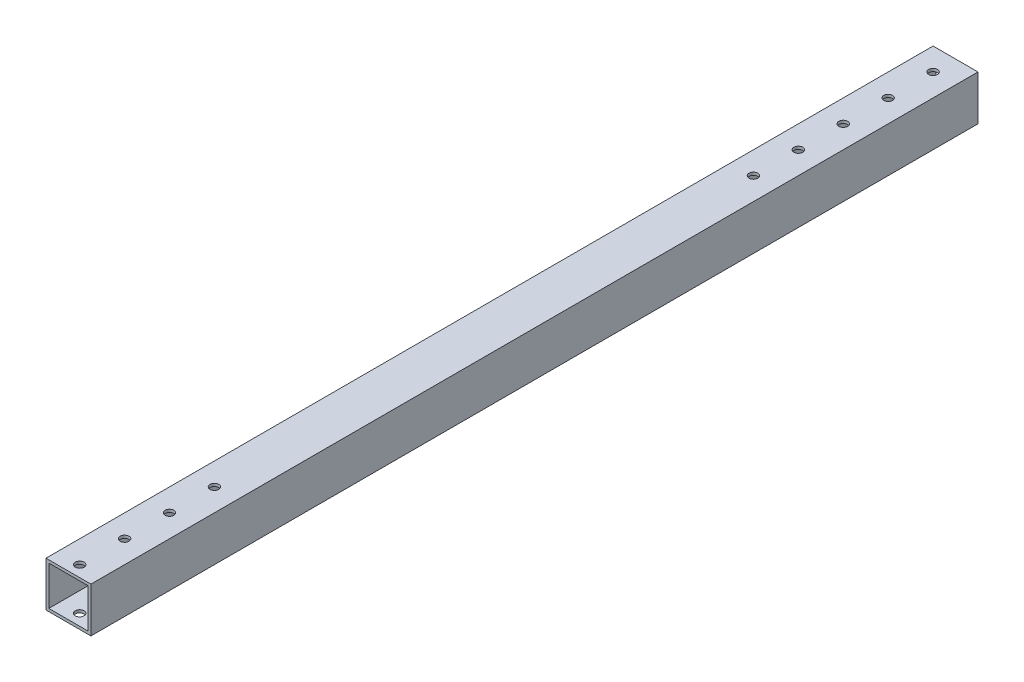
SolidWorks part; units mm, degrees
material "6061-T6 (SS)"
ref_plane "Front Plane" through (0, 0, 0) normal (0, 0, 1) x (1, 0, 0)
ref_plane "Top Plane" through (0, 0, 0) normal (0, 1, 0) x (1, 0, 0)
ref_plane "Right Plane" through (0, 0, 0) normal (1, 0, 0) x (0, 0, -1)
sketch "Sketch1" plane through (0, 0, 0) normal (0, 0, 1) x (1, 0, 0)
  line L1 (-12.7, -12.7) -> (12.7, -12.7)
  line L2 (-12.7, -12.7) -> (-12.7, 12.7)
  line L3 (-12.7, 12.7) -> (12.7, 12.7)
  line L4 (12.7, -12.7) -> (12.7, 12.7)
  line L5 (-12.7, -12.7) -> (12.7, 12.7) construction
  line L6 (-12.7, 12.7) -> (12.7, -12.7) construction
  point P0 (0, 0)
  dimension "D1" = 25.4
  dimension "D2" = 25.4
extrude "Boss-Extrude1" add sketch "Sketch1" along normal mid plane 501.65
shell "Shell1" thickness 1.5875 removed face at (0, 0, -250.825) removed face at (0, 0, 250.825)
sketch "Sketch3" plane through (0, 0, 0) normal (0, 1, 0) x (1, 0, 0)
  line L0 (12.7, 250.825) -> (-12.7, 250.825) construction
  circle A0 centre (0, 238.125) radius 2.4892
  circle A1 centre (0, 212.725) radius 2.4892
  circle A2 centre (0, 187.325) radius 2.4892
  circle A3 centre (0, 161.925) radius 2.4892
  circle A4 centre (0, 136.525) radius 2.4892
  circle A5 centre (0, 111.125) radius 2.4892 construction
  circle A6 centre (0, 85.725) radius 2.4892 construction
  circle A7 centre (0, 60.325) radius 2.4892 construction
  circle A8 centre (0, 34.925) radius 2.4892 construction
  circle A9 centre (0, 9.525) radius 2.4892 construction
  circle A10 centre (0, -15.875) radius 2.4892 construction
  circle A11 centre (0, -41.275) radius 2.4892 construction
  circle A12 centre (0, -66.675) radius 2.4892 construction
  circle A13 centre (0, -92.075) radius 2.4892 construction
  circle A14 centre (0, -117.475) radius 2.4892 construction
  circle A15 centre (0, -142.875) radius 2.4892 construction
  circle A16 centre (0, -168.275) radius 2.4892
  circle A17 centre (0, -193.675) radius 2.4892
  circle A18 centre (0, -219.075) radius 2.4892
  circle A19 centre (0, -244.475) radius 2.4892
  point P4 (0, 250.825)
  dimension "D1" = 4.9784
  dimension "D2" = 12.7
  dimension "D4" = 25.4
  dimension "D3" = 20
extrude "Cut-Extrude1" cut sketch "Sketch3" against normal through all both and the other way through all
